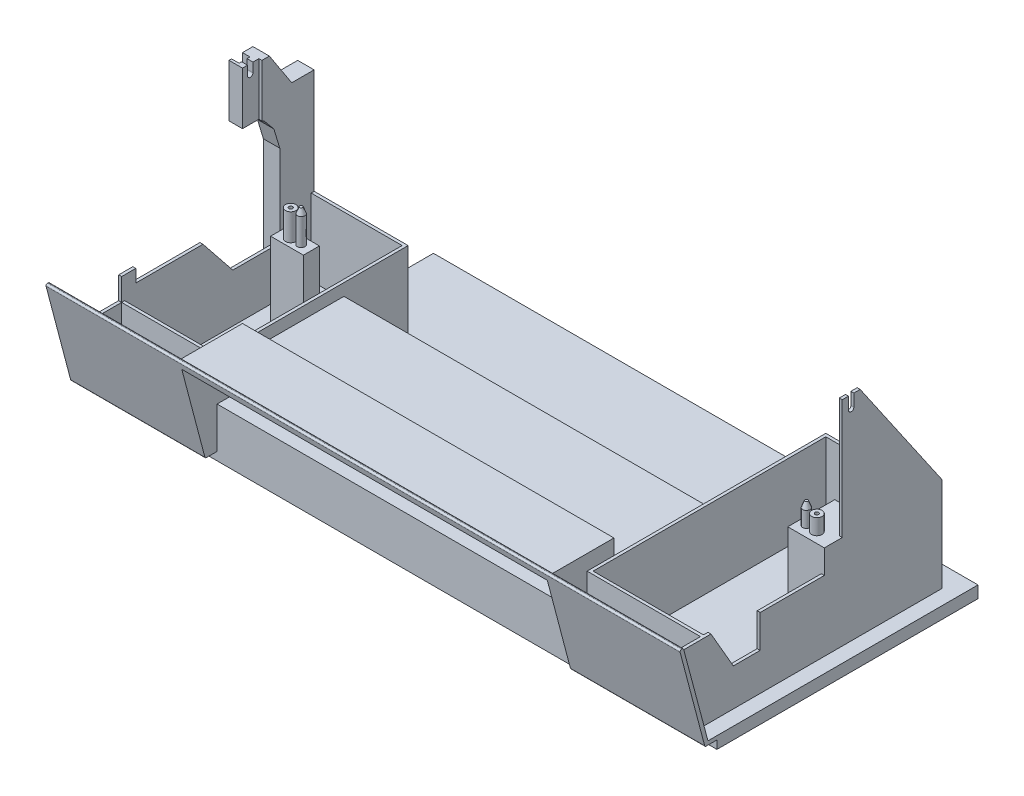
SolidWorks part; units mm, degrees
ref_plane "Alzado" through (0, 0, 0) normal (0, 0, 1) x (1, 0, 0)
ref_plane "Planta" through (0, 0, 0) normal (0, 1, 0) x (1, 0, 0)
ref_plane "Vista lateral" through (0, 0, 0) normal (1, 0, 0) x (0, 0, -1)
sketch "Croquis1" plane through (0, 0, 0) normal (0, 1, 0) x (1, 0, 0)
  line L1 (212.5, -92.5) -> (-212.5, -92.5)
  line L2 (212.5, -92.5) -> (212.5, 92.5)
  line L3 (212.5, 92.5) -> (-212.5, 92.5)
  line L4 (-212.5, -92.5) -> (-212.5, 92.5)
  line L5 (212.5, -92.5) -> (-212.5, 92.5) construction
  line L6 (212.5, 92.5) -> (-212.5, -92.5) construction
  line L7 (212.5, 92.5) -> (162.5, 92.5)
  line L8 (212.5, 92.5) -> (212.5, 82.5)
  line L9 (212.5, 82.5) -> (162.5, 82.5)
  line L10 (162.5, 92.5) -> (162.5, 82.5)
  line L11 (-212.5, 92.5) -> (-162.5, 92.5)
  line L12 (-212.5, 92.5) -> (-212.5, 47.5)
  line L13 (-212.5, 47.5) -> (-162.5, 47.5)
  line L14 (-162.5, 92.5) -> (-162.5, 47.5)
  point P0 (0, 0)
  dimension "D1" = 185
  dimension "D2" = 425
  dimension "D3" = 10
  dimension "D4" = 50
  dimension "D5" = 45
  dimension "D6" = 50
extrude "Saliente-Extruir3" add sketch "Croquis1" along normal blind 8 contours L3 L14 L13 L4 L1 L2 L9 L10 region at (4.3245, 0, 2.6524)
sketch "Croquis4" plane through (0, 0, 0) normal (0, -1, 0) x (1, 0, 0)
  line L1 (-212.5, 92.5) -> (212.5, 92.5)
  line L2 (-212.5, 92.5) -> (-212.5, 117.5)
  line L3 (-212.5, 117.5) -> (212.5, 117.5)
  line L4 (212.5, 92.5) -> (212.5, 117.5)
  dimension "D1" = 25
extrude "Saliente-Extruir5" add sketch "Croquis4" against normal blind 70 separate body
sketch "Croquis5" plane through (-212.5, 0, 0) normal (-1, 0, 0) x (0, 0, 1)
  line L0 (92.5, 8) -> (92.5, 5.5)
  line L2 (92.5, 8) -> (98.5, 8)
  line L3 (92.5, 70) -> (92.5, 0) construction
  line L4 (92.5, 5.5) -> (100.5, 5.5)
  line L10 (117.5, 0) -> (92.5, 0) construction
  line L11 (92.5, 70) -> (117.5, 70)
  line L12 (92.5, 70) -> (92.5, 0)
  line L13 (92.5, 0) -> (117.5, 0)
  line L14 (117.5, 70) -> (117.5, 0)
  line L15 (117.5, 70) -> (115, 70)
  line L16 (115, 70) -> (98.5, 8)
  line L17 (100.5, 5.5) -> (117.5, 70)
  line M12 (92.5, 0) -> (117.5, 0)
  line M13 (117.5, 0) -> (117.5, 70)
  line M15 (92.5, 70) -> (92.5, 0)
  dimension "D1" = 2.5
  dimension "D2" = 8
  dimension "D3" = 2.5
extrude "Cortar-Extruir5" cut sketch "Croquis5" against normal through all contours L16 L11 L2 M15 | L17 L4 M15 M12 M13 region at (-212.5, 44.9825, 100.4211) region at (-212.5, 22.1376, 110.4632)
fillet "Redondeo2" radius 1 3 edges at (0, 70, 115) (0, 70, 117.5) (0, 5.5, 100.5)
sketch "Croquis7" plane through (0, 0, 92.5) normal (0, 0, 1) x (1, 0, 0)
  line L1 (212.5, 0) -> (-212.5, 0) construction
  line L3 (-122.5, 0) -> (122.5, 0)
  line L4 (-122.5, 0) -> (-122.5, 65)
  line L5 (-122.5, 65) -> (122.5, 65)
  line L6 (122.5, 0) -> (122.5, 65)
  dimension "D2" = 65
  dimension "D3" = 245
extrude "Cortar-Extruir6" cut sketch "Croquis7" along normal blind 25
sketch "Croquis8" plane through (0, 8, 0) normal (0, 1, 0) x (1, 0, 0)
  line L1 (-122.5, -92.5) -> (122.5, -92.5)
  line L2 (-122.5, -92.5) -> (-122.5, -69.5)
  line L3 (-122.5, -69.5) -> (122.5, -69.5)
  line L4 (122.5, -92.5) -> (122.5, -69.5)
  dimension "D1" = 23
extrude "Saliente-Extruir6" add sketch "Croquis8" along normal blind 25
sketch "Croquis9" plane through (-122.5, 0, 0) normal (-1, 0, 0) x (0, 0, 1)
  line L2 (114.8023, 69.2572) -> (98.5, 8)
  line L4 (98.5, 8) -> (73.5, 8)
  line L5 (98.5, 8) -> (-47.5, 8) construction
  line L6 (73.5, 8) -> (73.5, 69.2572)
  line L7 (73.5, 69.2572) -> (114.8023, 69.2572)
  dimension "D1" = 25
extrude "Saliente-Extruir7" add sketch "Croquis9" along normal blind 2
sketch "Croquis10" plane through (122.5, 0, 0) normal (1, 0, 0) x (0, 0, -1)
  line L2 (-114.8023, 69.2572) -> (-98.5, 8)
  line L4 (-98.5, 8) -> (-73.5, 8)
  line L5 (-92.5, 8) -> (-69.5, 8) construction
  line L6 (-73.5, 8) -> (-73.5, 69.2572)
  line L7 (-73.5, 69.2572) -> (-114.8023, 69.2572)
  dimension "D1" = 25
extrude "Saliente-Extruir8" add sketch "Croquis10" along normal blind 2
sketch "Croquis13" plane through (-122.5, 0, 0) normal (1, 0, 0) x (0, 0, -1)
  line L2 (-114.8023, 69.2572) -> (-114.8023, 67.2572)
  line L5 (-114.8023, 69.2572) -> (-73.5, 69.2572)
  line L6 (-73.5, 69.2572) -> (-73.5, 67.2572)
  line L7 (-73.5, 69.2572) -> (-73.5, 33) construction
  line L8 (-114.8023, 67.2572) -> (-73.5, 67.2572)
  dimension "D1" = 2
extrude "Saliente-Extruir13" add sketch "Croquis13" along normal up to surface (245 mm away) up to face at (122.5, 39.0661, 97.4674)
sketch "Croquis15" plane through (0, 8, 0) normal (0, 1, 0) x (1, 0, 0)
  line L1 (212.5, -98.5) -> (212.5, 82.5) construction
  line L2 (212.5, -73.5) -> (212.5, -71.5)
  line L15 (124.5, -91.5) -> (202.5, -91.5)
  line L21 (124.5, -98.5) -> (124.5, -91.5)
  line L22 (124.5, -98.5) -> (124.5, -73.5) construction
  line L26 (202.5, -91.5) -> (202.5, 68.5)
  line L28 (126.5, -89.5) -> (200.5, -89.5)
  line L30 (202.5, 68.5) -> (124.5, 68.5)
  line L31 (124.5, -91.5) -> (124.5, 68.5)
  line L32 (124.5, 68.5) -> (124.5, 66.5) construction
  line L33 (124.5, 66.5) -> (126.5, 66.5) construction
  line L34 (126.5, 66.5) -> (126.5, -89.5)
  line L35 (126.5, 66.5) -> (200.5, 66.5)
  line L36 (200.5, 66.5) -> (200.5, -89.5)
  dimension "D2" = 160
  dimension "D1" = 7
  dimension "D3" = 2
  dimension "D4" = 2
extrude "Saliente-Extruir15" add sketch "Croquis15" along normal blind 51 contours L15 L26 L30 L31 | L28 L36 L35 L34
sketch "Croquis16" plane through (0, 8, 0) normal (0, 1, 0) x (1, 0, 0)
  line L1 (-122.5, -69.5) -> (122.5, -69.5)
  line L2 (-122.5, -69.5) -> (-122.5, -5.5)
  line L3 (-122.5, -5.5) -> (122.5, -5.5)
  line L4 (122.5, -69.5) -> (122.5, -5.5)
  dimension "D1" = 64
extrude "Saliente-Extruir16" add sketch "Croquis16" along normal blind 43
sketch "Croquis17" plane through (0, 8, 0) normal (0, 1, 0) x (1, 0, 0)
  line L1 (122.5, -5.5) -> (124.5, -5.5)
  line L2 (122.5, -5.5) -> (122.5, -73.5)
  line L3 (122.5, -73.5) -> (124.5, -73.5)
  line L4 (124.5, -5.5) -> (124.5, -73.5)
  line L6 (124.5, -73.5) -> (124.5, 68.5) construction
  line L7 (124.5, -73.5) -> (122.5, -73.5) construction
  dimension "D1" = 68
extrude "Saliente-Extruir18" add sketch "Croquis17" along normal up to surface (43 mm away) up to face at (0, 51, 37.5)
sketch "Croquis18" plane through (202.5, 0, 0) normal (1, 0, 0) x (0, 0, -1)
  line L0 (-91.5, 8) -> (-98.5, 8)
  line L1 (-98.5, 8) -> (-112.0726, 59)
  line L2 (-114.8023, 69.2572) -> (-98.5, 8) construction
  line L3 (-112.0726, 59) -> (-91.5, 59)
  line L4 (-91.5, 59) -> (-91.5, 8)
extrude "Saliente-Extruir21" add sketch "Croquis18" against normal blind 2
sketch "Croquis20" plane through (0, 59, 0) normal (0, 1, 0) x (1, 0, 0)
  line L1 (200.5, -91.5) -> (202.5, -91.5)
  line L2 (200.5, -91.5) -> (200.5, 68.5)
  line L3 (200.5, 68.5) -> (202.5, 68.5)
  line L4 (202.5, -91.5) -> (202.5, 68.5)
extrude "Saliente-Extruir22" add sketch "Croquis20" along normal blind 100
sketch "Croquis21" plane through (202.5, 0, 0) normal (1, 0, 0) x (0, 0, -1)
  line L0 (-91.5, 59) -> (-86.5, 59)
  line L3 (-71.5, 33) -> (-86.5, 59)
  line L4 (-71.5, 33) -> (-53.5, 33)
  line L5 (-53.5, 33) -> (-53.5, 55)
  line L6 (-53.5, 55) -> (-10.5, 55)
  line L7 (-10.5, 55) -> (-10.5, 71)
  line L8 (-10.5, 71) -> (1.5, 71)
  line L9 (1.5, 71) -> (1.5, 151)
  line L11 (13.5, 151) -> (68.5, 71)
  line L12 (68.5, 159) -> (68.5, 8) construction
  line L13 (-91.5, 59) -> (-91.5, 159)
  line L14 (-91.5, 159) -> (68.5, 159)
  line L15 (68.5, 159) -> (68.5, 71)
  line L16 (1.5, 151) -> (5.7, 151)
  line L17 (5.7, 151) -> (5.7, 142.8)
  line L18 (13.5, 151) -> (9.3, 151)
  line L19 (9.3, 151) -> (9.3, 142.8)
  line L20 (-86.5, 59) -> (-86.5, 33) construction
  line L21 (-86.5, 33) -> (-71.5, 33) construction
  arc A0 (5.7, 142.8) -> (9.3, 142.8) centre (7.5, 142.8) ccw
  dimension "D12" = 6
  dimension "D1" = 5
  dimension "D2" = 18
  dimension "D3" = 22
  dimension "D4" = 43
  dimension "D5" = 16
  dimension "D6" = 12
  dimension "D7" = 80
  dimension "D8" = 12
  dimension "D9" = 4.2
  dimension "D10" = 8.2
  dimension "D11" = 4.2
extrude "Cortar-Extruir7" cut sketch "Croquis21" against normal blind 2
sketch "Croquis22" plane through (0, 8, 0) normal (0, 1, 0) x (1, 0, 0)
  line L1 (-124.5, -73.5) -> (-122.5, -73.5)
  line L2 (-124.5, -73.5) -> (-124.5, -5.5)
  line L3 (-124.5, -5.5) -> (-122.5, -5.5)
  line L4 (-122.5, -73.5) -> (-122.5, -5.5)
extrude "Saliente-Extruir23" add sketch "Croquis22" along normal up to surface (43 mm away) up to face at (41.5, 51, 49.5)
sketch "Croquis23" plane through (0, 8, 0) normal (0, 1, 0) x (1, 0, 0)
  line L0 (-124.5, -91.5) -> (-124.5, -89.5) construction
  line L1 (-124.5, -98.5) -> (-124.5, -91.5) construction
  line L2 (-124.5, -5.5) -> (-124.5, -98.5) construction
  line L3 (-124.5, -89.5) -> (-126.5, -89.5) construction
  line L4 (-124.5, -91.5) -> (-189.5, -91.5)
  line L5 (-124.5, -91.5) -> (-124.5, 37.5)
  line L6 (-124.5, 37.5) -> (-189.5, 37.5)
  line L7 (-189.5, -91.5) -> (-189.5, 37.5)
  line L9 (-126.5, -89.5) -> (-187.5, -89.5)
  line L10 (-126.5, -89.5) -> (-126.5, 35.5)
  line L11 (-126.5, 35.5) -> (-187.5, 35.5)
  line L12 (-187.5, -89.5) -> (-187.5, 35.5)
  dimension "D1" = 7
  dimension "D2" = 129
  dimension "D3" = 65
  dimension "D4" = 2
  dimension "D5" = 2
  dimension "D6" = 125
  dimension "D7" = 61
extrude "Saliente-Extruir24" add sketch "Croquis23" along normal up to surface (51 mm away) up to face at (171.8846, 59, 43.2804)
sketch "Croquis26" plane through (-189.5, 0, 0) normal (-1, 0, 0) x (0, 0, 1)
  line L0 (91.5, 8) -> (98.5, 8)
  line L5 (91.5, 59) -> (91.5, 8)
  line L6 (91.5, 59) -> (112.0726, 59)
  line L7 (114.8023, 69.2572) -> (98.5, 8) construction
  line L8 (112.0726, 59) -> (98.5, 8)
extrude "Saliente-Extruir26" add sketch "Croquis26" against normal blind 2
sketch "Croquis27" plane through (0, 51, 0) normal (0, 1, 0) x (1, 0, 0)
  line L7 (-189.5, 37.5) -> (-187.5, 37.5)
  line L8 (-189.5, 37.5) -> (-189.5, -91.5)
  line L9 (-189.5, -91.5) -> (-187.5, -91.5)
  line L10 (-187.5, 37.5) -> (-187.5, -91.5)
extrude "Saliente-Extruir27" add sketch "Croquis27" along normal blind 150
sketch "Croquis28" plane through (-189.5, 0, 0) normal (-1, 0, 0) x (0, 0, 1)
  line L0 (91.5, 59) -> (91.5, 74)
  line L1 (91.5, 201) -> (91.5, 59) construction
  line L2 (91.5, 74) -> (82, 74)
  line L3 (82, 74) -> (82, 65.5)
  line L4 (82, 65.5) -> (37, 65.5)
  line L7 (17, 40.5) -> (37, 65.5)
  line L8 (-37.5, 40.5) -> (-14.5, 40.5) construction
  line L9 (-37.5, 201) -> (-37.5, 8) construction
  line L10 (17, 40.5) -> (-14.5, 40.5)
  line L11 (-14.5, 40.5) -> (-14.5, 95.5)
  line L13 (-37.5, 129.5) -> (-37.5, 201)
  line L17 (-22.5, 129.5) -> (-7.5, 152.5)
  line L18 (-22.5, 129.5) -> (-37.5, 129.5)
  line L19 (-14.5, 95.5) -> (-10.5263, 108.6789)
  line L20 (-10.5263, 108.6789) -> (-4.1622, 116.3418)
  line L22 (-37.5, 201) -> (91.5, 201)
  line L23 (91.5, 201) -> (91.5, 74)
  line L24 (-7.5, 152.5) -> (-2.5, 152.5)
  line L29 (-37.5, 129.5) -> (-37.5, 201)
  line L30 (91.5, 201) -> (91.5, 74)
  line L32 (-4.1622, 116.3418) -> (-2.5, 117.3138)
  line L33 (-2.5, 152.5) -> (-2.5, 117.3138)
  line M3 (91.5, 59) -> (91.5, 201)
  line M4 (91.5, 201) -> (-37.5, 201)
  line M5 (-37.5, 201) -> (-37.5, 8)
  dimension "D5" = 23
  dimension "D1" = 15
  dimension "D2" = 9.5
  dimension "D3" = 8.5
  dimension "D4" = 45
  dimension "D6" = 55
extrude "Cortar-Extruir9" cut sketch "Croquis28" against normal blind 2 contours L20 L19 L11 L10 L7 L4 L3 L2 L18 L17 L24 M3 M4 M5 region at (-189.5, 131.8782, 31.3357)
sketch "Croquis29" plane through (-189.5, 0, 0) normal (-1, 0, 0) x (0, 0, 1)
  line L0 (-14.5, 95.5) -> (-10.5263, 108.6789)
  line L1 (-37.5, 8) -> (-14.5, 8)
  line L2 (-37.5, 8) -> (-37.5, 129.5)
  line L5 (-10.5263, 108.6789) -> (-4.1622, 116.3418)
  line L6 (-4.1622, 116.3418) -> (-2.5, 117.3138)
  line L7 (-22.5, 129.5) -> (-7.5, 152.5)
  line L8 (-7.5, 152.5) -> (1.5, 152.5)
  line L11 (-14.5, 95.5) -> (-14.5, 8)
  line L12 (-37.5, 129.5) -> (-22.5, 129.5)
  line L13 (1.5, 152.5) -> (1.5, 146.3)
  line L15 (5.1, 146.3) -> (5.1, 152.5)
  line L16 (5.1, 152.5) -> (8.5, 152.5)
  line L17 (8.5, 152.5) -> (8.5, 117.3138)
  line L18 (8.5, 117.3138) -> (-2.5, 117.3138)
  arc A0 (1.5, 146.3) -> (5.1, 146.3) centre (3.3, 146.3) ccw
  dimension "D1" = 121.5
  dimension "D2" = 23
  dimension "D3" = 9
  dimension "D4" = 6.2
  dimension "D5" = 3.6
  dimension "D6" = 3.4
extrude "Saliente-Extruir28" add sketch "Croquis29" along normal blind 9
sketch "Croquis30" plane through (-198.5, 0, 0) normal (-1, 0, 0) x (0, 0, 1)
  line L0 (1.5, 152.5) -> (-0.5, 152.5)
  line L1 (1.5, 152.5) -> (-7.5, 152.5) construction
  line L2 (-0.5, 152.5) -> (-0.5, 146.1)
  line L3 (-0.5, 146.1) -> (2.3, 143.3)
  line L4 (4.3, 143.3) -> (2.3, 143.3)
  line L6 (4.3, 143.3) -> (6.8, 146.1)
  line L7 (5.1, 152.5) -> (6.8, 152.5)
  line L9 (8.5, 152.5) -> (5.1, 152.5) construction
  line L10 (6.8, 152.5) -> (6.8, 146.1)
  line L12 (-0.5, 152.5) -> (1.5, 152.5)
  line L13 (5.1, 152.5) -> (5.1, 146.3)
  line L14 (1.5, 146.3) -> (1.5, 152.5)
  arc A1 (5.1, 146.3) -> (1.5, 146.3) centre (3.3, 146.3) cw
  point P10 (3.3, 143.3)
  line M9 (8.5, 152.5) -> (5.1, 152.5)
  line M10 (5.1, 152.5) -> (5.1, 146.3)
  arc M11 (5.1, 146.3) -> (1.5, 146.3) centre (3.3, 146.3) cw
  line M12 (1.5, 146.3) -> (1.5, 152.5)
  line M13 (1.5, 152.5) -> (-7.5, 152.5)
  dimension "D1" = 2
  dimension "D2" = 6.4
  dimension "D5" = 1.7
  dimension "D6" = 6.4
extrude "Cortar-Extruir10" cut sketch "Croquis30" against normal blind 5 and the other way blind 1 contours L10 L2 M9 M10 M11 M12 M13 region at (-198.5, 149.4, 1.3826)
sketch "Croquis33" plane through (0, 8, 0) normal (0, 1, 0) x (1, 0, 0)
  line L0 (-124.5, 37.5) -> (-124.5, -2.3) construction
  line L1 (-124.5, -5.5) -> (-124.5, 37.5) construction
  line L2 (-124.5, -2.3) -> (-149.5, -2.3) construction
  line L3 (-149.5, -7.65) -> (-149.5, 3.05)
  line L4 (-149.5, 3.05) -> (-171.5, 3.05)
  line L5 (-171.5, 3.05) -> (-171.5, -7.65)
  line L6 (-171.5, -7.65) -> (-149.5, -7.65)
  point P9 (-149.5, -2.3)
  dimension "D1" = 39.8
  dimension "D2" = 25
  dimension "D3" = 5.35
  dimension "D4" = 22
extrude "Saliente-Extruir29" add sketch "Croquis33" along normal blind 55.5
sketch "Croquis34" plane through (0, 63.5, 0) normal (0, 1, 0) x (1, 0, 0)
  line L0 (-159.9, 3) -> (-158.9, 3)
  line L1 (-171.5, -7.65) -> (-171.5, -2.3) construction
  line L2 (-158.9, 3) -> (-156.4, 3)
  line L3 (-171.5, 3.05) -> (-171.5, -7.65) construction
  line L4 (-171.5, -2.3) -> (-163.4, -2.3) construction
  line L6 (-156.4, -2.3) -> (-163.4, -2.3) construction
  circle A3 centre (-163.4, -2.3) radius 1.25
  circle A4 centre (-163.4, -2.3) radius 3.5
  circle A5 centre (-156.4, -2.3) radius 2.5
  dimension "D3" = 7
  dimension "D1" = 2.5
  dimension "D5" = 5
  dimension "D2" = 1
  dimension "D4" = 2.5
extrude "Saliente-Extruir30" add sketch "Croquis34" along normal blind 18 contours A3 | A5 region at (-166.801, 63.5, 2.3)
sketch "Croquis36" plane through (200.5, 0, 0) normal (-1, 0, 0) x (0, 0, 1)
  line L1 (10.5, 71) -> (-21, 71)
  line L2 (10.5, 71) -> (10.5, 8)
  line L3 (10.5, 8) -> (-21, 8)
  line L4 (-21, 71) -> (-21, 8)
  line L5 (-66.5, 8) -> (89.5, 8) construction
  dimension "D1" = 63
  dimension "D2" = 31.5
extrude "Saliente-Extruir34" add sketch "Croquis36" along normal blind 22.5
sketch "Croquis37" plane through (0, 71, 0) normal (0, 1, 0) x (1, 0, 0)
  line L0 (202.5, 1.5) -> (202.5, -3.5) construction
  line L1 (202.5, -10.5) -> (202.5, 1.5) construction
  line L2 (202.5, -3.5) -> (194, -3.5) construction
  line L3 (194, -3.5) -> (190.5, -3.5) construction
  line L4 (187, -3.5) -> (186, -3.5)
  line L5 (186, -3.5) -> (183.5, -3.5)
  circle A0 centre (190.5, -3.5) radius 3.5
  circle A1 centre (183.5, -3.5) radius 2.5
  circle A2 centre (190.5, -3.5) radius 1.25
  dimension "D4" = 7
  dimension "D7" = 5
  dimension "D8" = 2.5
  dimension "D1" = 5
  dimension "D2" = 8.5
  dimension "D3" = 3.5
  dimension "D5" = 1
  dimension "D6" = 2.5
extrude "Saliente-Extruir35" add sketch "Croquis37" along normal blind 10.5 contours A0 A2 | A1 region at (181.0707, 71, 3.5) region at (190.5, 71, 0.099)
sketch "Croquis38" plane through (0, 81.5, 0) normal (0, 1, 0) x (1, 0, 0)
  circle A0 centre (183.5, -3.5) radius 1
  dimension "D1" = 2
extrude "Saliente-Extruir36" add sketch "Croquis38" along normal blind 4
loft "Recubrir2" add section edge at (183.5, 85.5, 4.5) section edge at (183.5, 81.5, 6) connector at (183.5119, 85.5, 4.4999) connector at (183.6915, 81.5, 5.9927)
sketch "Croquis39" plane through (0, 81.5, 0) normal (0, 1, 0) x (1, 0, 0)
  circle A0 centre (-156.4, -2.3) radius 1
  dimension "D1" = 2
extrude "Saliente-Extruir37" add sketch "Croquis39" along normal blind 4
loft "Recubrir3" add section edge at (-156.4, 81.5, 4.8) section edge at (-156.4, 85.5, 3.3) connector at (-157.8859, 81.5, 0.2895) connector at (-156.6487, 85.5, 1.3314)
